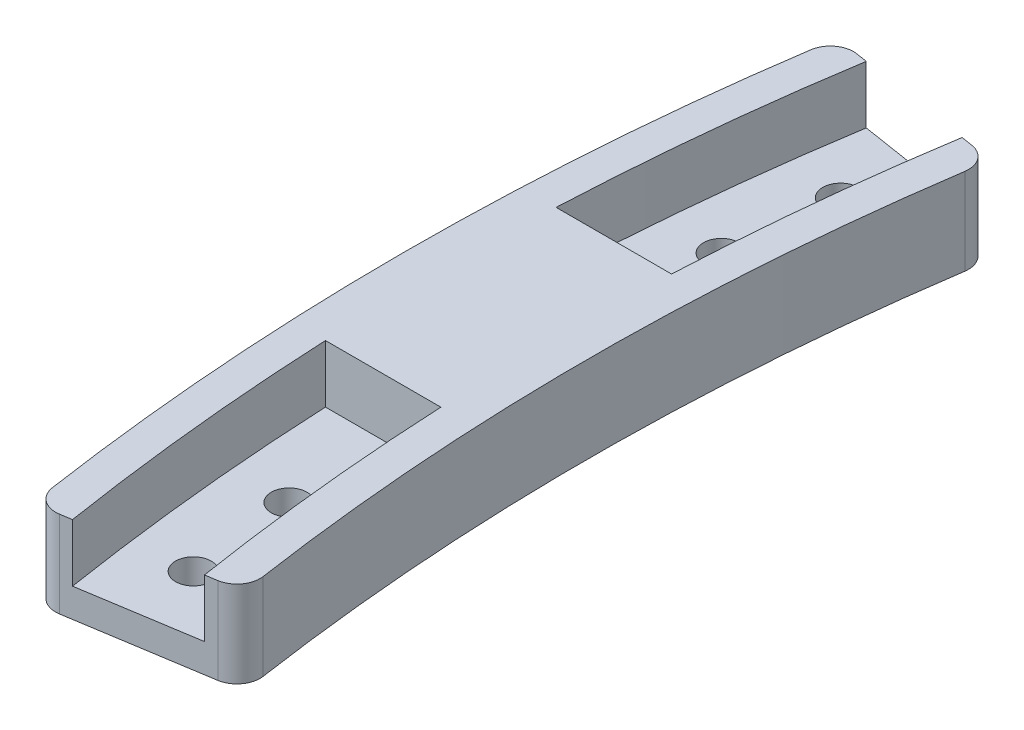
SolidWorks part; units mm, degrees
ref_plane "Front Plane" through (0, 0, 0) normal (0, 0, 1) x (1, 0, 0)
ref_plane "Top Plane" through (0, 0, 0) normal (0, 1, 0) x (1, 0, 0)
ref_plane "Right Plane" through (0, 0, 0) normal (1, 0, 0) x (0, 0, -1)
sketch "Sketch1" plane through (0, 0, 0) normal (0, 1, 0) x (1, 0, 0)
  line L0 (0, 0) -> (-217.2914, -34.4156) construction
  line L1 (0, 0) -> (-217.2914, 34.4156) construction
  line L2 (0, 0) -> (-215, 0) construction
  line L3 (-217.2914, 34.4156) -> (-207.4146, 32.8512)
  line L4 (-207.4146, -32.8512) -> (-217.2914, -34.4156)
  line L5 (0, 0) -> (-220.2545, -34.8849) construction
  line L6 (0, 0) -> (-220.2545, 34.8849) construction
  line L7 (-220.2545, 34.8849) -> (-204.4515, 32.3819)
  line L8 (-220.2545, -34.8849) -> (-204.4515, -32.3819)
  arc A0 (-217.2914, 34.4156) -> (-217.2914, -34.4156) centre (0, 0) ccw
  arc A1 (-207.4146, 32.8512) -> (-207.4146, -32.8512) centre (0, 0) ccw
  arc A2 (-212.353, -33.6334) -> (-212.353, 33.6334) centre (0, 0) cw construction
  arc A4 (-204.4515, 32.3819) -> (-204.4515, -32.3819) centre (0, 0) ccw
  arc A5 (-220.2545, 34.8849) -> (-220.2545, -34.8849) centre (0, 0) ccw
  dimension "D1" = 220
  dimension "D2" = 210
  dimension "D3" = 5
  dimension "D5" = 3
  dimension "D6" = 3
  dimension "D4" = 18
extrude "Boss-Extrude1" add sketch "Sketch1" along normal blind 10 contours A1 L3 A0 L4 | L7 A5 L8 A0 | A4 L7 A1 L8 region at (-220.5936, 0, 0) region at (-214.1555, 0, 0) region at (-207.6472, 0, 0)
ref_plane "Plane1" through (-215, 0, 0) normal (1, 0, 0) x (0, 0, -1)
sketch "Sketch15" plane through (0, 10, 0) normal (0, 1, 0) x (1, 0, 0)
  line L0 (-207.4146, -32.8512) -> (-217.2914, -34.4156) construction
  line L1 (-205, 10) -> (-225, 10)
  line L2 (-205, 10) -> (-205, -10)
  line L3 (-205, -10) -> (-225, -10)
  line L4 (-225, 10) -> (-225, -10)
  line L5 (-205, 10) -> (-225, -10) construction
  line L6 (-205, -10) -> (-225, 10) construction
  line L7 (-217.2914, 34.4156) -> (-207.4146, 32.8512) construction
  line L8 (-207.4146, -32.8512) -> (-217.2914, -34.4156)
  line L9 (-217.2914, 34.4156) -> (-207.4146, 32.8512)
  arc A2 (-207.4146, 32.8512) -> (-207.4146, -32.8512) centre (0, 0) ccw construction
  arc A3 (-217.2914, 34.4156) -> (-217.2914, -34.4156) centre (0, 0) ccw construction
  arc A4 (-207.4146, 32.8512) -> (-207.4146, -32.8512) centre (0, 0) ccw
  arc A5 (-217.2914, 34.4156) -> (-217.2914, -34.4156) centre (0, 0) ccw
  point P0 (-215, 0)
  line M5 (-220.2545, -34.8849) -> (-204.4515, -32.3819)
  line M7 (-204.4515, 32.3819) -> (-220.2545, 34.8849)
  dimension "D1" = 20
  dimension "D2" = 20
extrude "Cut-Extrude1" cut sketch "Sketch15" against normal blind 5 contours A5 L1 A4 M7 | L3 A5 A4 M5 region at (-213.8328, 10, -21.8433) region at (-213.8328, 10, 21.8433)
ref_plane "Plane2" through (-215, 0, 0) normal (-1, 0, 0) x (0, 0, 1)
sketch "Sketch12" plane through (0, 0, 0) normal (0, 1, 0) x (1, 0, 0)
  line L0 (0, 0) -> (-214.1819, -18.7385) construction
  line L1 (0, 0) -> (-213.1606, -28.0631) construction
  line L2 (0, 0) -> (-215, 0) construction
  line L3 (0, 0) -> (-215, 0) construction
  line L4 (0, 0) -> (-214.1819, 18.7385) construction
  line L5 (0, 0) -> (-213.1606, 28.0631) construction
  arc A0 (-212.353, 33.6334) -> (-212.353, -33.6334) centre (0, 0) ccw construction
  dimension "D1" = 10
  dimension "D2" = 15
hole_wizard "Ø3.1 (3.1) Diameter Hole2" positions "Sketch18" profile "Sketch17" hole size "Ø3.1" standard "ISO" end condition through all
sketch "Sketch18" plane through (0, 0, 0) normal (0, -1, 0) x (-1, 0, 0)
  point P0 (213.1606, -28.0631)
  point P3 (214.1819, -18.7385)
  point P6 (214.1819, 18.7385)
  point P9 (213.1606, 28.0631)
sketch "Sketch17" plane through (-213.1606, 0, 28.0631) normal (1, 0, 0) x (0, 0, -1)
  line L0 (0, 0) -> (0, 10)
  line L1 (0, 10) -> (1.55, 10)
  line L2 (1.55, 10) -> (1.55, 0)
  line L5 (1.55, 0) -> (0, 0)
  line L11 (0, -6.35) -> (0, 107.95) construction
  dimension "Thru Hole Dia." = 3.1
  dimension "Thru Hole Depth" = 10
fillet "Fillet1" radius 2 4 edges at (-220.2545, 5, -34.8849) (-204.4515, 5, -32.3819) (-220.2545, 5, 34.8849) (-204.4515, 5, 32.3819)
sketch "Sketch19" plane through (0, 0, 0) normal (0, -1, 0) x (1, 0, 0)
  line L2 (-218.2702, -34.5706) -> (-206.4174, -32.6933)
  line L3 (-206.4174, 32.6933) -> (-218.2702, 34.5706)
  line L4 (-218.2702, -34.5706) -> (-206.4174, -32.6933)
  line L5 (-206.4174, 32.6933) -> (-218.2702, 34.5706)
  arc A6 (-220.5612, 32.8902) -> (-220.5612, -32.8902) centre (0, 0) ccw
  arc A7 (-220.5612, -32.8902) -> (-218.2702, -34.5706) centre (-218.5831, -32.5952) ccw
  arc A8 (-206.4174, -32.6933) -> (-204.752, -30.424) centre (-206.7303, -30.7179) ccw
  arc A9 (-204.752, 30.424) -> (-204.752, -30.424) centre (0, 0) ccw
  arc A10 (-204.752, 30.424) -> (-206.4174, 32.6933) centre (-206.7303, 30.7179) ccw
  arc A11 (-218.2702, 34.5706) -> (-220.5612, 32.8902) centre (-218.5831, 32.5952) ccw
  arc A12 (-220.5612, 32.8902) -> (-220.5612, -32.8902) centre (0, 0) ccw
  arc A13 (-220.5612, -32.8902) -> (-218.2702, -34.5706) centre (-218.5831, -32.5952) ccw
  arc A14 (-206.4174, -32.6933) -> (-204.752, -30.424) centre (-206.7303, -30.7179) ccw
  arc A15 (-204.752, 30.424) -> (-204.752, -30.424) centre (0, 0) ccw
  arc A16 (-204.752, 30.424) -> (-206.4174, 32.6933) centre (-206.7303, 30.7179) ccw
  arc A17 (-218.2702, 34.5706) -> (-220.5612, 32.8902) centre (-218.5831, 32.5952) ccw
  dimension "D1" = 0
extrude "Cut-Extrude2" cut sketch "Sketch19" against normal blind 2.5
